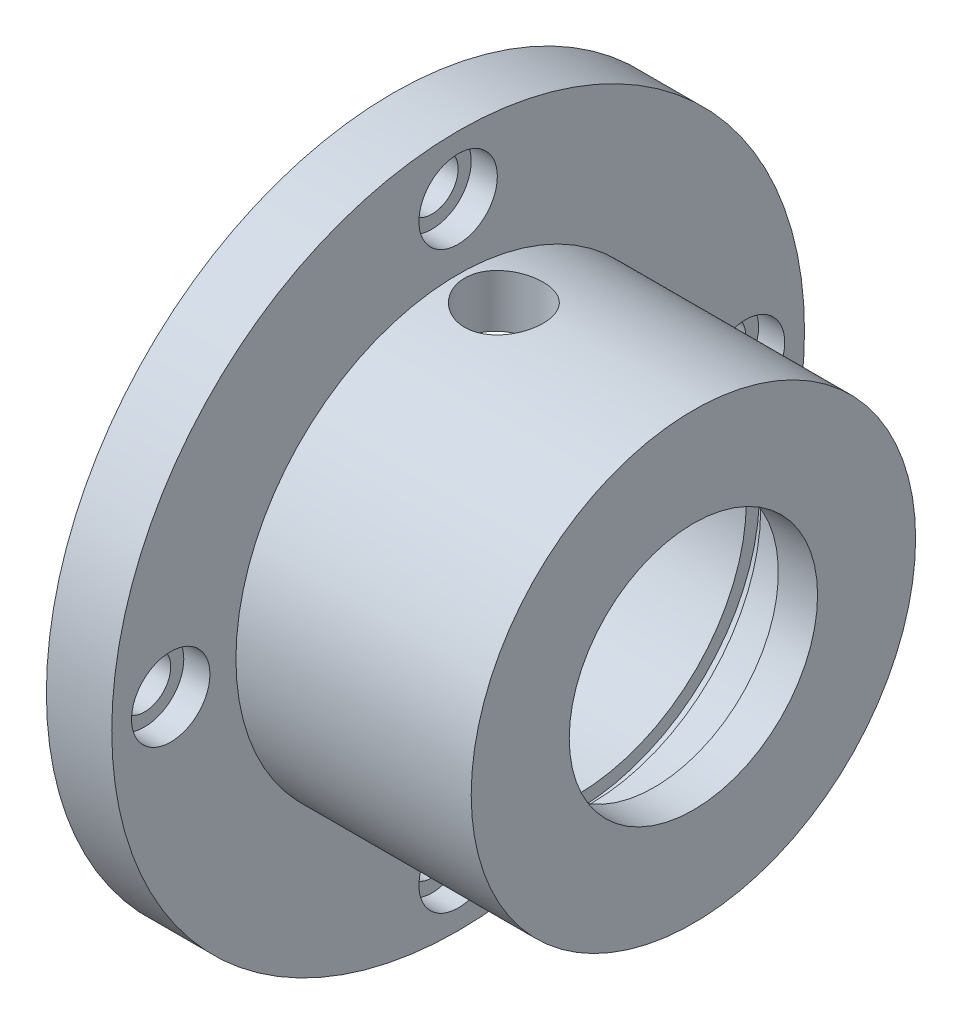
SolidWorks part; units mm, degrees
ref_plane "Front Plane" through (0, 0, 0) normal (0, 0, 1) x (1, 0, 0)
ref_plane "Top Plane" through (0, 0, 0) normal (0, 1, 0) x (1, 0, 0)
ref_plane "Right Plane" through (0, 0, 0) normal (1, 0, 0) x (0, 0, -1)
sketch "Sketch1" plane through (0, 0, 0) normal (1, 0, 0) x (0, 0, -1)
  circle A0 centre (0, 0) radius 26.5
  circle A2 centre (0, -21.9877) radius 2
  circle A3 centre (-21.9877, 0) radius 2
  circle A4 centre (0, 21.9877) radius 2
  circle A5 centre (21.9877, 0) radius 2
  point P14 (0, 0)
  dimension "D1" = 53
  dimension "D2" = 4
  dimension "D3" = 4
extrude "Boss-Extrude1" add sketch "Sketch1" along normal mid plane 23
sketch "Sketch2" plane through (11.5, 0, 0) normal (1, 0, 0) x (0, 0, -1)
  circle A0 centre (0, 0) radius 17
  circle A1 centre (0, 0) radius 26.5
  circle M3 centre (0, 21.9877) radius 2
  circle M4 centre (0, -21.9877) radius 2
  circle M5 centre (0, 0) radius 26.5
  circle M6 centre (-21.9877, 0) radius 2
  circle M7 centre (21.9877, 0) radius 2
  dimension "D1" = 53
  dimension "D3" = 34
extrude "Cut-Extrude1" cut sketch "Sketch2" against normal blind 18 contours A0 M5 M4 M6 M7 M3 region at (11.5, 0, 25.7505)
sketch "Sketch3" plane through (-11.5, 0, 0) normal (-1, 0, 0) x (0, 0, 1)
  circle A0 centre (0, 0) radius 13
  dimension "D1" = 26
extrude "Cut-Extrude2" cut sketch "Sketch3" against normal blind 20
sketch "Sketch4" plane through (8.5, 0, 0) normal (-1, 0, 0) x (0, 0, 1)
  circle A0 centre (0, 0) radius 9.5
  dimension "D1" = 19
extrude "Cut-Extrude3" cut sketch "Sketch4" against normal blind 20
ref_plane "Plane1" through (3.1, 0, 0) normal (-1, 0, 0) x (0, 0, 1)
sketch "Sketch5" plane through (3.1, 0, 0) normal (-1, 0, 0) x (0, 0, 1)
  circle A0 centre (0, 0) radius 14
  dimension "D1" = 28
extrude "Cut-Extrude4" cut sketch "Sketch5" against normal mid plane 1.1
ref_axis "Axis1" through (26.7383, 0, 0) along (-1, 0, 0)
sketch "Sketch6" plane through (0, 0, 0) normal (0, 1, 0) x (1, 0, 0)
  line L0 (26.7383, 0) -> (-32.37, 0) construction
  line L1 (11.5, -17) -> (11.5, 17) construction
  circle A0 centre (-3, 0) radius 3
  dimension "D1" = 14.5
extrude "Cut-Extrude5" cut sketch "Sketch6" along normal blind 33
ref_plane "Plane3" through (0, 17, 0) normal (0, 1, 0) x (1, 0, 0)
sketch "Sketch8" plane through (0, 17, 0) normal (0, 1, 0) x (1, 0, 0)
  line L1 (0.1411, -6) -> (-6.1411, -6)
  line L2 (0.1411, -6) -> (0.1411, 6)
  line L3 (0.1411, 6) -> (-6.1411, 6)
  line L4 (-6.1411, -6) -> (-6.1411, 6)
  line L5 (0.1411, -6) -> (-6.1411, 6) construction
  line L6 (0.1411, 6) -> (-6.1411, -6) construction
  point P0 (-3, 0)
  dimension "D1" = 12
extrude "Cut-Extrude6" [suppressed] cut sketch "Sketch8" against normal blind 1
sketch "Sketch9" plane through (-6.5, 0, 0) normal (1, 0, 0) x (0, 0, -1)
  circle A0 centre (0, 21.9877) radius 3
  circle A1 centre (21.9877, 0) radius 3
  circle A2 centre (0, -21.9877) radius 3
  circle A3 centre (-21.9877, 0) radius 3
  point P12 (0, 0)
  dimension "D1" = 4
extrude "Cut-Extrude7" cut sketch "Sketch9" against normal blind 2
